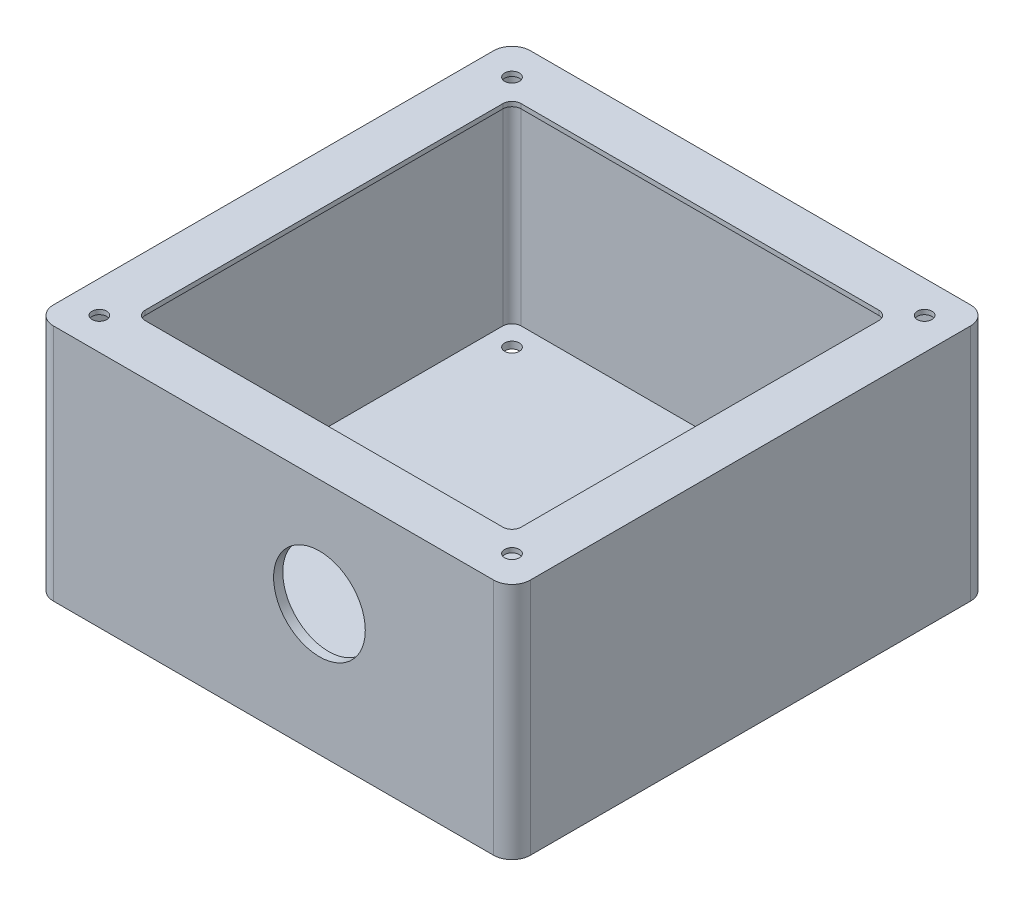
SolidWorks part; units mm, degrees
material "S-Glass Fiber"
ref_plane "Front Plane" through (0, 0, 0) normal (0, 0, 1) x (1, 0, 0)
ref_plane "Top Plane" through (0, 0, 0) normal (0, 1, 0) x (1, 0, 0)
ref_plane "Right Plane" through (0, 0, 0) normal (1, 0, 0) x (0, 0, -1)
sketch "Sketch1" plane through (0, 0, 0) normal (0, 1, 0) x (1, 0, 0)
  line L0 (45, 45) -> (-45, 45) construction
  line L1 (48, -50) -> (-48, -50)
  line L2 (50, -48) -> (50, 48)
  line L3 (48, 50) -> (-48, 50)
  line L4 (-50, -48) -> (-50, 48)
  line L5 (50, -50) -> (-50, 50) construction
  line L6 (50, 50) -> (-50, -50) construction
  line L7 (-45, -45) -> (-45, 45) construction
  line L8 (45, -45) -> (-45, -45) construction
  line L9 (45, -45) -> (45, 45) construction
  line L10 (50, -50) -> (-50, -50) construction
  line L11 (-50, -50) -> (-50, 50) construction
  line L12 (50, -50) -> (50, 50) construction
  line L13 (50, 50) -> (-50, 50) construction
  circle A0 centre (-45, 45) radius 1.6
  circle A1 centre (45, 45) radius 1.6
  circle A2 centre (45, -45) radius 1.6
  circle A3 centre (-45, -45) radius 1.6
  arc A4 (-48, -50) -> (-50, -48) centre (-48, -48) cw
  arc A5 (48, -50) -> (50, -48) centre (48, -48) ccw
  arc A6 (50, 48) -> (48, 50) centre (48, 48) ccw
  arc A7 (-48, 50) -> (-50, 48) centre (-48, 48) ccw
  point P0 (0, 0)
  dimension "D4" = 3.2
  dimension "D5" = 3.2
  dimension "D6" = 3.2
  dimension "D7" = 3.2
  dimension "D8" = 2
  dimension "D1" = 100
  dimension "D2" = 100
  dimension "D3" = 5
extrude "Boss-Extrude1" add sketch "Sketch1" along normal blind 1.5
sketch "Sketch2" plane through (0, 1.5, 0) normal (0, 1, 0) x (1, 0, 0)
  line L9 (48, 50) -> (-48, 50) construction
  line L10 (-50, 48) -> (-50, -48) construction
  line L11 (-48, -50) -> (48, -50) construction
  line L12 (50, -48) -> (50, 48) construction
  line L13 (48, 50) -> (-48, 50)
  line L14 (-50, 48) -> (-50, -48)
  line L15 (-48, -50) -> (48, -50)
  line L16 (50, -48) -> (50, 48)
  line L17 (48, 52) -> (-48, 52)
  line L19 (-52, 48) -> (-52, -48)
  line L35 (-48, -52) -> (48, -52)
  line L36 (52, -48) -> (52, 48)
  arc A0 (-48, 50) -> (-50, 48) centre (-48, 48) ccw construction
  arc A1 (-50, -48) -> (-48, -50) centre (-48, -48) ccw construction
  arc A2 (48, -50) -> (50, -48) centre (48, -48) ccw construction
  arc A3 (50, 48) -> (48, 50) centre (48, 48) ccw construction
  arc A4 (-48, 50) -> (-50, 48) centre (-48, 48) ccw
  arc A5 (-50, -48) -> (-48, -50) centre (-48, -48) ccw
  arc A6 (48, -50) -> (50, -48) centre (48, -48) ccw
  arc A7 (50, 48) -> (48, 50) centre (48, 48) ccw
  arc A8 (-48, 52) -> (-52, 48) centre (-48, 48) ccw
  arc A9 (-52, -48) -> (-48, -52) centre (-48, -48) ccw
  arc A10 (48, -52) -> (52, -48) centre (48, -48) ccw
  arc A11 (52, 48) -> (48, 52) centre (48, 48) ccw
  dimension "D1" = 2
extrude "Boss-Extrude10" add sketch "Sketch2" along normal blind 50 separate body
sketch "Sketch5" plane through (0, 0, 52) normal (0, 0, 1) x (1, 0, 0)
  line L0 (-48, 51.5) -> (48, 1.5) construction
  line L1 (0, 26.5) -> (0, 1.5) construction
  line L2 (-48, 1.5) -> (48, 1.5) construction
  line L3 (0, 26.5) -> (0, 41.5) construction
  line L4 (0, 41.5) -> (30, 41.5) construction
  line L5 (30, 41.5) -> (30, 16.5) construction
  line L7 (30, 29) -> (10, 29) construction
  circle A0 centre (10, 29) radius 10
extrude "Cut-Extrude1" cut sketch "Sketch5" against normal blind 10
sketch "Sketch6" plane through (0, 51.5, 0) normal (0, 1, 0) x (1, 0, 0)
  line L3 (-39, -41) -> (39, -41)
  line L4 (48, 52) -> (-48, 52)
  line L5 (-52, 48) -> (-52, -48)
  line L6 (-48, -52) -> (48, -52)
  line L7 (52, -48) -> (52, 48)
  line L8 (48, 52) -> (-48, 52)
  line L9 (-52, 48) -> (-52, -48)
  line L10 (-48, -52) -> (48, -52)
  line L11 (52, -48) -> (52, 48)
  line L12 (-41, -39) -> (-41, 39)
  line L13 (-39, 41) -> (39, 41)
  line L14 (41, -39) -> (41, 39)
  line L15 (-41, -41) -> (41, 41) construction
  line L16 (-41, 41) -> (41, -41) construction
  circle A0 centre (-45, 45) radius 1.6 construction
  circle A1 centre (45, 45) radius 1.6 construction
  circle A2 centre (45, -45) radius 1.6 construction
  circle A3 centre (-45, -45) radius 1.6 construction
  arc A4 (52, 48) -> (48, 52) centre (48, 48) ccw
  arc A5 (-48, 52) -> (-52, 48) centre (-48, 48) ccw
  arc A6 (-52, -48) -> (-48, -52) centre (-48, -48) ccw
  arc A7 (48, -52) -> (52, -48) centre (48, -48) ccw
  arc A8 (52, 48) -> (48, 52) centre (48, 48) ccw
  arc A9 (-48, 52) -> (-52, 48) centre (-48, 48) ccw
  arc A10 (-52, -48) -> (-48, -52) centre (-48, -48) ccw
  arc A11 (48, -52) -> (52, -48) centre (48, -48) ccw
  circle A12 centre (-45, 45) radius 1.6
  circle A13 centre (45, 45) radius 1.6
  circle A14 centre (45, -45) radius 1.6
  circle A15 centre (-45, -45) radius 1.6
  arc A16 (-39, -41) -> (-41, -39) centre (-39, -39) cw
  arc A17 (39, -41) -> (41, -39) centre (39, -39) ccw
  arc A18 (39, 41) -> (41, 39) centre (39, 39) cw
  arc A19 (-41, 39) -> (-39, 41) centre (-39, 39) cw
  point P28 (0, 0)
  dimension "D2" = 2
  dimension "D1" = 0
extrude "Boss-Extrude11" add sketch "Sketch6" along normal blind 1
extrude "Boss-Extrude12" add sketch "Sketch2<6>" against normal blind 1
sketch "Sketch2<6>" plane through (0, 1.5, 0) normal (0, 1, 0) x (1, 0, 0) same geometry as "Sketch2"
